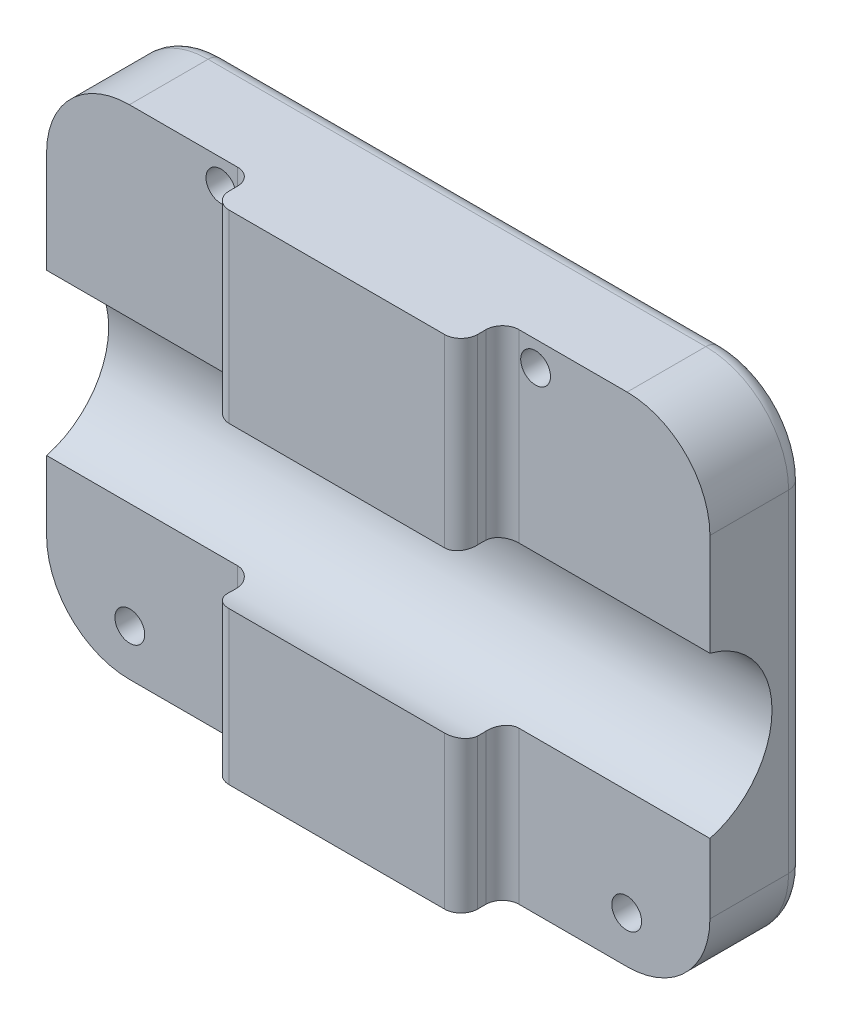
SolidWorks part; units mm, degrees
ref_plane "前视基准面" through (0, 0, 0) normal (0, 0, 1) x (1, 0, 0)
ref_plane "上视基准面" through (0, 0, 0) normal (0, 1, 0) x (1, 0, 0)
ref_plane "右视基准面" through (0, 0, 0) normal (1, 0, 0) x (0, 0, -1)
other "Configuration Table"
sketch "草图1" plane through (0, 0, 0) normal (0, 0, 1) x (1, 0, 0)
  line L1 (0, 0) -> (80.1, 0)
  line L2 (0, 0) -> (0, -60.1)
  line L3 (0, -60.1) -> (80.1, -60.1)
  line L4 (80.1, 0) -> (80.1, -60.1)
  dimension "D1" = 80.1
  dimension "D2" = 60.1
extrude "凸台-拉伸1" add sketch "草图1" along normal blind 28
sketch "草图2" plane through (80.1, 0, 0) normal (1, 0, 0) x (0, 0, -1)
  line L0 (-14, 0) -> (-14, -60.1)
  line L1 (-28, 0) -> (0, 0) construction
  line L2 (-28, -60.1) -> (0, -60.1) construction
  line L3 (-28, -32) -> (0, -32)
  line L4 (-28, -60.1) -> (-28, 0) construction
  line L5 (0, -60.1) -> (0, 0) construction
  circle A0 centre (-14, -32) radius 10
  dimension "D2" = 20
  dimension "D1" = 32
extrude "切除-拉伸1" cut sketch "草图2" against normal blind 108 contours L3 A0 L0 | L3 A0 L0 | L0 A0 L3 | L0 A0 L3 region at (80.1, -27.7559, 9.7559) region at (80.1, -27.7559, 18.2441) region at (80.1, -36.2441, 9.7559) region at (80.1, -36.2441, 18.2441)
sketch "草图3" plane through (0, 0, 0) normal (0, 1, 0) x (1, 0, 0)
  line L0 (0, -14) -> (80.1, -14) construction
  line L1 (40.05, 0) -> (40.05, -28) construction
  line L2 (0, -11.5) -> (25.05, -11.5)
  line L3 (25.05, -11.5) -> (25.05, -16.5)
  line L4 (80.1, 0) -> (0, 0)
  line L5 (0, 0) -> (0, -28)
  line L6 (0, -28) -> (80.1, -28)
  line L7 (80.1, -28) -> (80.1, 0)
  line L8 (80.1, 0) -> (0, 0)
  line L9 (0, 0) -> (0, -28)
  line L10 (0, -28) -> (80.1, -28)
  line L11 (80.1, -28) -> (80.1, 0)
  line L12 (25.05, -16.5) -> (55.05, -16.5)
  line L13 (55.05, -16.5) -> (55.05, -11.5)
  line L14 (55.05, -11.5) -> (80.1, -11.5)
  point P9 (40.05, -28)
  line M13 (0, 0) -> (0, -28)
  line M14 (0, -28) -> (80.1, -28)
  line M15 (80.1, -28) -> (80.1, 0)
  dimension "D2" = 5
  dimension "D3" = 30
  dimension "D1" = 0
extrude "切除-拉伸2" cut sketch "草图3" against normal blind 80 contours L14 L13 L12 L3 L2 M13 M14 M15 region at (40.05, 0, 20.4861)
fillet "圆角1" radius 2 8 edges at (55.05, -11.1588, 16.5) (55.05, -50.8912, 16.5) (55.05, -50.8912, 11.5) (55.05, -11.1588, 11.5) (25.05, -11.1588, 16.5) (25.05, -50.8912, 16.5) (25.05, -50.8912, 11.5) (25.05, -11.1588, 11.5)
sketch "草图4" plane through (0, 0, 0) normal (0, 0, -1) x (-1, 0, 0)
  line L0 (-59.05, -3) -> (-21.05, -3)
  line L1 (-70.05, -54.5) -> (-10.05, -54.5)
  line L2 (-40.05, 0) -> (-40.05, -60.1) construction
  line L4 (0, -60.1) -> (0, 0)
  line L5 (0, 0) -> (-80.1, 0)
  line L6 (-80.1, 0) -> (-80.1, -60.1)
  line L7 (-80.1, -60.1) -> (0, -60.1)
  line L8 (0, -60.1) -> (0, 0)
  line L9 (0, 0) -> (-80.1, 0)
  line L10 (-80.1, 0) -> (-80.1, -60.1)
  line L11 (-80.1, -60.1) -> (0, -60.1)
  circle A0 centre (-70.05, -54.5) radius 1.8
  circle A1 centre (-10.05, -54.5) radius 1.8
  circle A2 centre (-21.05, -3) radius 1.8
  circle A3 centre (-59.05, -3) radius 1.8
  dimension "D2" = 3.6
  dimension "D3" = 60
  dimension "D1" = 0
  dimension "D4" = 38
  dimension "D5" = 51.5
  dimension "D6" = 3
extrude "切除-拉伸3" cut sketch "草图4" against normal blind 80 contours A0 | A1 | A2 | A3 region at (21.05, -1.2509, 0) region at (10.05, -52.7509, 0) region at (71.7991, -54.5, 0)
fillet "圆角2" radius 10 4 edges at (80.1, -60.1, 5.75) (80.1, 0, 5.75) (0, -60.1, 5.75) (0, 0, 5.75)
fillet "圆角3" radius 2 8 edges at (77.1711, -2.9289, 0) (80.1, -30.05, 0) (77.1711, -57.1711, 0) (40.05, -60.1, 0) (2.9289, -57.1711, 0) (0, -30.05, 0) (2.9289, -2.9289, 0) (40.05, 0, 0)
